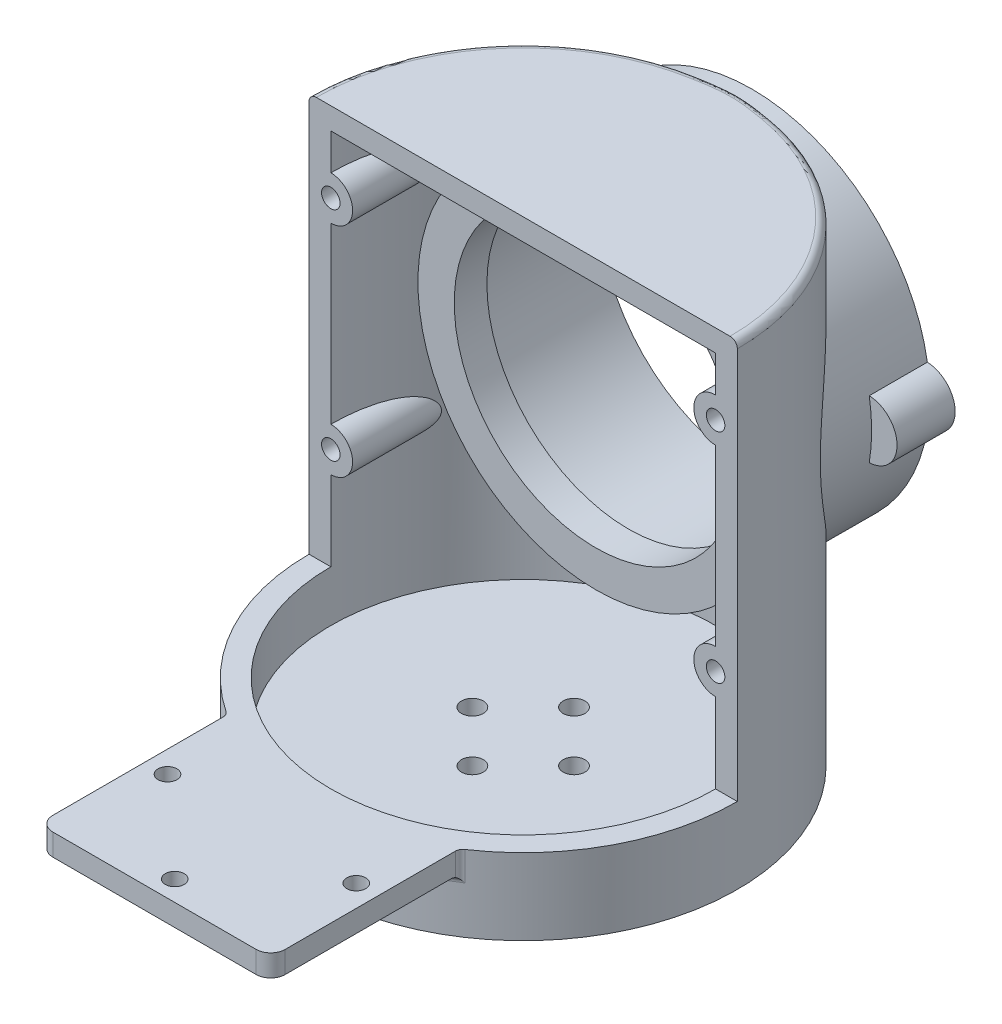
SolidWorks part; units mm, degrees
ref_plane "Спереди" through (0, 0, 0) normal (0, 0, 1) x (1, 0, 0)
ref_plane "Сверху" through (0, 0, 0) normal (0, 1, 0) x (1, 0, 0)
ref_plane "Справа" through (0, 0, 0) normal (1, 0, 0) x (0, 0, -1)
sketch "Эскиз3" plane through (0, 0, 0) normal (1, 0, 0) x (0, 0, -1)
  line L0 (0, 68.2882) -> (0, 0) construction
  line L1 (0, 0) -> (29.5, 0)
  line L2 (29.5, 0) -> (29.5, 66)
  line L3 (29.5, 66) -> (0, 66)
  line L4 (0, 66) -> (0, 63)
  line L5 (0, 63) -> (26.5, 63)
  line L6 (26.5, 63) -> (26.5, 4)
  line L7 (26.5, 4) -> (0, 4)
  line L8 (0, 4) -> (0, 0)
  dimension "D1" = 29.5
  dimension "D2" = 66
  dimension "D3" = 3
  dimension "D4" = 4
  dimension "D5" = 26.5
revolve "Повернуть2" add sketch "Эскиз3" angle 360 about L0
sketch "Эскиз4" plane through (0, 66, 0) normal (0, 1, 0) x (1, 0, 0)
  line L0 (-29.5, 0) -> (29.5, 0)
  circle A0 centre (0, 0) radius 29.5 construction
  arc A1 (29.5, 0) -> (-29.5, 0) centre (0, 0) cw
extrude "Вырез-Вытянуть1" cut sketch "Эскиз4" against normal blind 55
sketch "Эскиз5" plane through (0, 0, 0) normal (0, -1, 0) x (1, 0, 0)
  circle A0 centre (0, 0) radius 19.5
  circle A1 centre (0, 0) radius 29.5
  dimension "D1" = 59
  dimension "D2" = 39
extrude "Вырез-Вытянуть2" cut sketch "Эскиз5" against normal blind 0.5
sketch "Эскиз6" plane through (0, 0, 0) normal (0, -1, 0) x (1, 0, 0)
  circle A0 centre (7, 0) radius 1.5
  dimension "D1" = 3
  dimension "D2" = 7
extrude "Вырез-Вытянуть3" cut sketch "Эскиз6" against normal up to surface (4 mm away) up to face at (0, 4, 26.5)
pattern_circular "Круговой массив1" count 4 every 90 about axis through (0, 68.2882, 0) along (0, 1, 0) of "Вырез-Вытянуть3"
sketch "Эскиз7" plane through (0, 0, 0) normal (0, 0, 1) x (1, 0, 0)
  circle A0 centre (0, 41) radius 19.5
  circle A1 centre (0, 41) radius 24.5
  dimension "D1" = 49
  dimension "D2" = 39
  dimension "D3" = 41
extrude "Бобышка-Вытянуть1" add sketch "Эскиз7" against normal blind 21.5 from offset 10 offset against normal yes
sketch "Эскиз8" plane through (0, 0, -31.5) normal (0, 0, -1) x (-1, 0, 0)
  circle A0 centre (0, 41) radius 21
  dimension "D1" = 42
  dimension "D2" = 41
extrude "Вырез-Вытянуть4" cut sketch "Эскиз8" against normal blind 17
sketch "Эскиз9" plane through (0, 11, 0) normal (0, 1, 0) x (1, 0, 0)
  line L0 (-16, -24.7841) -> (-16, -50.7841)
  line L1 (-16, -50.7841) -> (16, -50.7841)
  line L2 (16, -50.7841) -> (16, -24.7841)
  line L3 (0, 0) -> (0, -50.7841) construction
  arc A0 (16, -24.7841) -> (-16, -24.7841) centre (0, 0) cw
  arc A1 (-29.5, 0) -> (29.5, 0) centre (0, 0) ccw construction
  dimension "D1" = 26
  dimension "D2" = 32
extrude "Бобышка-Вытянуть2" add sketch "Эскиз9" against normal blind 3
fillet "Скругление1" radius 2 2 edges at (16, 9.5, 50.7841) (-16, 9.5, 50.7841)
fillet "Скругление2" radius 1 4 edges at (16, 9.5, 24.7841) (0, 8, 29.5) (-16, 9.5, 24.7841) (0, 66, -29.5)
sketch "Эскиз11" plane through (0, 0, 0) normal (0, 0, 1) x (1, 0, 0)
  line L0 (-26.5, 63) -> (-26.5, 11) construction
  line L1 (26.5, 11) -> (26.5, 63) construction
  line L3 (-26.5, 25) -> (26.5, 25) construction
  line L4 (-26.5, 25) -> (-26.5, 55) construction
  line L5 (-26.5, 55) -> (26.5, 55) construction
  line L6 (26.5, 25) -> (26.5, 55) construction
  circle A0 centre (-26.5, 55) radius 3
  circle A1 centre (-26.5, 25) radius 3
  circle A2 centre (26.5, 25) radius 3
  circle A3 centre (26.5, 55) radius 3
  point P12 (0, 25)
  point P15 (26.5, 40)
  dimension "D1" = 6
  dimension "D2" = 6
  dimension "D3" = 6
  dimension "D4" = 6
  dimension "D5" = 30
  dimension "D6" = 40
extrude "Бобышка-Вытянуть3" add sketch "Эскиз11" against normal up to surface (12.2474 mm away) up to face at (0.4697, 37.9438, -4.7854)
hole_wizard "Сверло под метчик  спиральное M2.52" positions "Эскиз15" profile "Эскиз16" hole size "M2.5x0.45" standard "Ansi Metric"
sketch "Эскиз15" plane through (0, 0, 0) normal (0, 0, 1) x (1, 0, 0)
  point P0 (-26.5, 55)
  point P3 (26.5, 55)
  point P6 (26.5, 25)
  point P9 (-26.5, 25)
sketch "Эскиз16" plane through (-26.5, 55, 0) normal (1, 0, 0) x (0, -1, 0)
  line L0 (0, 0) -> (0, 5.7661)
  line L1 (0, 5.7661) -> (1.275, 5)
  line L2 (1.275, 5) -> (1.275, 0)
  line L5 (1.275, 0) -> (0, 0)
  line L10 (0, 5.7661) -> (-1.275, 5) construction
  line L11 (0, -6.35) -> (0, 107.95) construction
  dimension "Диаметр отверстия" = 2.55
  dimension "Глубина отверстия" = 5
  dimension "Угол заточки сверла" = 118
sketch "Эскиз17" plane through (0, 11, 0) normal (0, 1, 0) x (1, 0, 0)
  circle A0 centre (-13, -36) radius 1.3
  circle A1 centre (0, -48) radius 1.3
  circle A2 centre (13, -36) radius 1.3
  dimension "D1" = 2.6
  dimension "D2" = 36
  dimension "D3" = 12
  dimension "D4" = 13
  dimension "D5" = 26
extrude "Вырез-Вытянуть5" cut sketch "Эскиз17" against normal up to surface (3 mm away) up to face at (0, 8, 42.7385)
sketch "Эскиз18" plane through (0, 0, -31.5) normal (0, 0, -1) x (-1, 0, 0)
  circle A0 centre (0, 41) radius 24 construction
  arc A1 (-24.1719, 44.9963) -> (-24.1719, 37.0037) centre (0, 41) ccw
  arc A3 (-3.9963, 16.8281) -> (3.9963, 16.8281) centre (0, 17) ccw
  arc A4 (24.1719, 37.0037) -> (24.1719, 44.9963) centre (24, 41) ccw
  arc A5 (-24.1719, 44.9963) -> (-24.1719, 37.0037) centre (-24, 41) ccw
  arc A6 (-3.9963, 16.8281) -> (3.9963, 16.8281) centre (0, 41) ccw
  arc A7 (24.1719, 37.0037) -> (24.1719, 44.9963) centre (0, 41) ccw
  dimension "D1" = 48
  dimension "D2" = 8
  dimension "D3" = 24.5
extrude "Бобышка-Вытянуть4" add sketch "Эскиз18" against normal blind 8
hole_wizard "Отверстие с зазором M21" positions "Эскиз19" profile "Эскиз21" hole size "M2" standard "Ansi Metric"
sketch "Эскиз19" plane through (0, 0, -31.5) normal (0, 0, -1) x (-1, 0, 0)
  point P0 (-24, 41)
  point P3 (0, 17)
  point P6 (24, 41)
sketch "Эскиз21" plane through (24, 41, -31.5) normal (1, 0, 0) x (0, 1, 0)
  line L0 (0, 0) -> (0, 5.721)
  line L1 (0, 5.721) -> (1.2, 5)
  line L2 (1.2, 5) -> (1.2, 0)
  line L5 (1.2, 0) -> (0, 0)
  line L10 (0, 5.721) -> (-1.2, 5) construction
  line L11 (0, -6.35) -> (0, 107.95) construction
  dimension "Диаметр отверстия" = 2.4
  dimension "Глубина отверстия" = 5
  dimension "Угол заточки сверла" = 118
